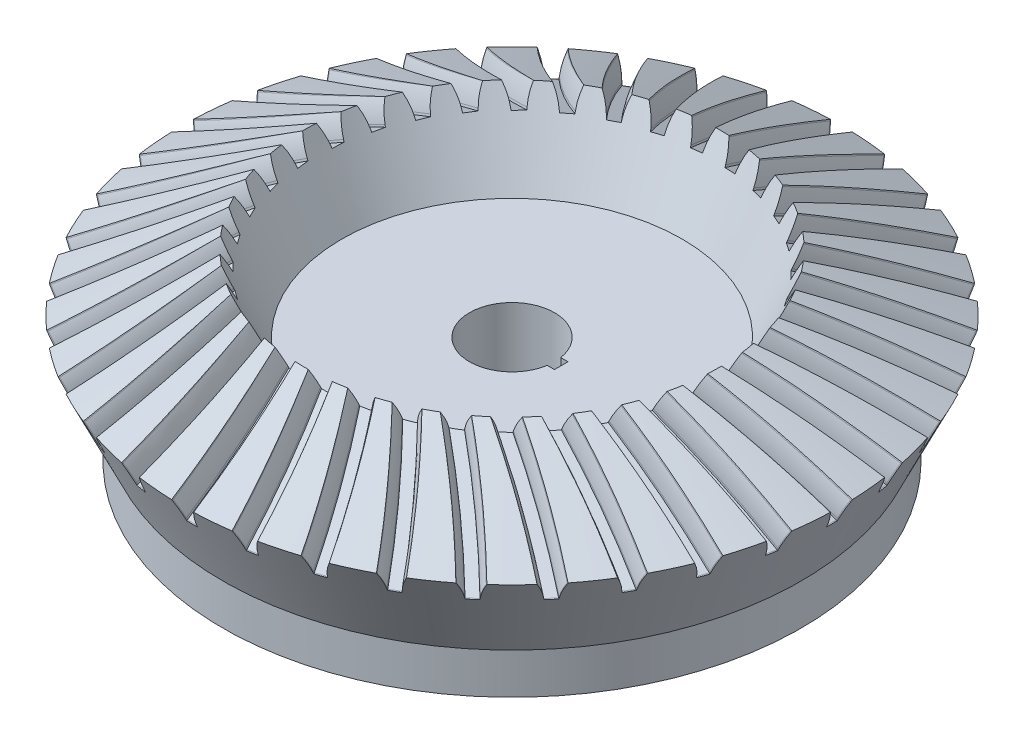
SolidWorks part; units mm, degrees
ref_plane "Alzado" through (0, 0, 0) normal (0, 0, 1) x (1, 0, 0)
ref_plane "Planta" through (0, 0, 0) normal (0, 1, 0) x (1, 0, 0)
ref_plane "Vista lateral" through (0, 0, 0) normal (1, 0, 0) x (0, 0, -1)
sketch "Croquis1" plane through (0, 0, 0) normal (0, 0, 1) x (1, 0, 0)
  line L0 (0, 0) -> (0, 40)
  line L1 (0, 40) -> (50, 40)
  line L2 (50, 40) -> (60.7108, 62.5894)
  line L3 (60.7108, 62.5894) -> (96.8537, 45.4522)
  line L4 (96.8537, 45.4522) -> (85, 20.4522)
  line L5 (85, 20.4522) -> (85, 8.4522)
  line L6 (85, 8.4522) -> (20, 8.4522)
  line L7 (20, 8.4522) -> (20, 0)
  line L8 (20, 0) -> (0, 0)
  line L9 (0, 0) -> (0, 72.7393) construction
  dimension "D1" = 40
  dimension "D2" = 50
  dimension "D3" = 25
  dimension "D4" = 40
  dimension "D5" = 25
  dimension "D6" = 65
  dimension "D7" = 20
  dimension "D8" = 12
  dimension "D9" = 115.368
  dimension "D10" = 90
revolve "Revolución1" add sketch "Croquis1" angle 360 about L9
ref_plane "Plano1" through (-61.4806, -29.151, 0) normal (-0.9036, -0.4284, 0) x (0, 0, 1)
sketch "Croquis2" plane through (-61.4806, -29.151, 0) normal (-0.9036, -0.4284, 0) x (0, 0, 1)
  line L0 (0, 82.5645) -> (0, 69.4382) construction
  line L4 (-1.5606, 76.0014) -> (1.5606, 76.0014)
  line L5 (1.5606, 76.0014) -> (1.6242, 76.5837)
  line L6 (3.1099, 82.2592) -> (3.5456, 83.2805)
  line L7 (-3.1099, 82.2592) -> (-3.5456, 83.2805)
  line L8 (-1.5606, 76.0014) -> (-1.6242, 76.5837)
  line L9 (-3.5456, 83.2805) -> (3.5456, 83.2805)
  arc A0 (1.6242, 76.5837) -> (3.1099, 82.2592) centre (21.5059, 74.4113) cw
  arc A1 (-1.6242, 76.5837) -> (-3.1099, 82.2592) centre (-21.5059, 74.4113) ccw
  ellipse E0 centre (0, 41.0694) end of major axis (-96.8537, 41.0694) minor radius 41.4951 construction
  point P18 (0, 76.0014)
  dimension "D1" = 20
ref_plane "Plano3" through (-35.3731, 74.6032, 0) normal (-0.4284, 0.9036, 0) x (0.9036, 0.4284, 0)
sketch "Croquis8" plane through (-35.3731, 74.6032, 0) normal (-0.4284, 0.9036, 0) x (0.9036, 0.4284, 0)
  line L0 (-68.0415, 0) -> (-67.7599, 0.0272)
  line L1 (-25.9179, 6.887) -> (-25.6112, 6.9584)
  arc A0 (-67.7599, 0.0272) -> (-25.9179, 6.887) centre (-98.4964, 318.5476) ccw
  dimension "D1" = 320
sweep "Cortar-Barrer3" cut profiles "Croquis2" path "Croquis8"
pattern_circular "MatrizC4" count 36 over 360 about axis through (0, 45.4522, 0) along (0, 1, 0) of "Cortar-Barrer3" reverse direction yes
sketch "Croquis10" plane through (0, 0, 0) normal (0, -1, 0) x (1, 0, 0)
  line L1 (12.3409, -1.9879) -> (14.4671, -1.9879)
  line L3 (12.3409, 1.9879) -> (14.4671, 1.9879)
  line L4 (14.4671, -1.9879) -> (14.4671, 1.9879)
  circle A0 centre (0, 0) radius 20
  arc A1 (12.3409, 1.9879) -> (12.3409, -1.9879) centre (0, 0) ccw
  point P4 (12.5, 0)
extrude "Cortar-Extruir4" cut sketch "Croquis10" against normal blind 150 contours A1 L1 L4 L3
